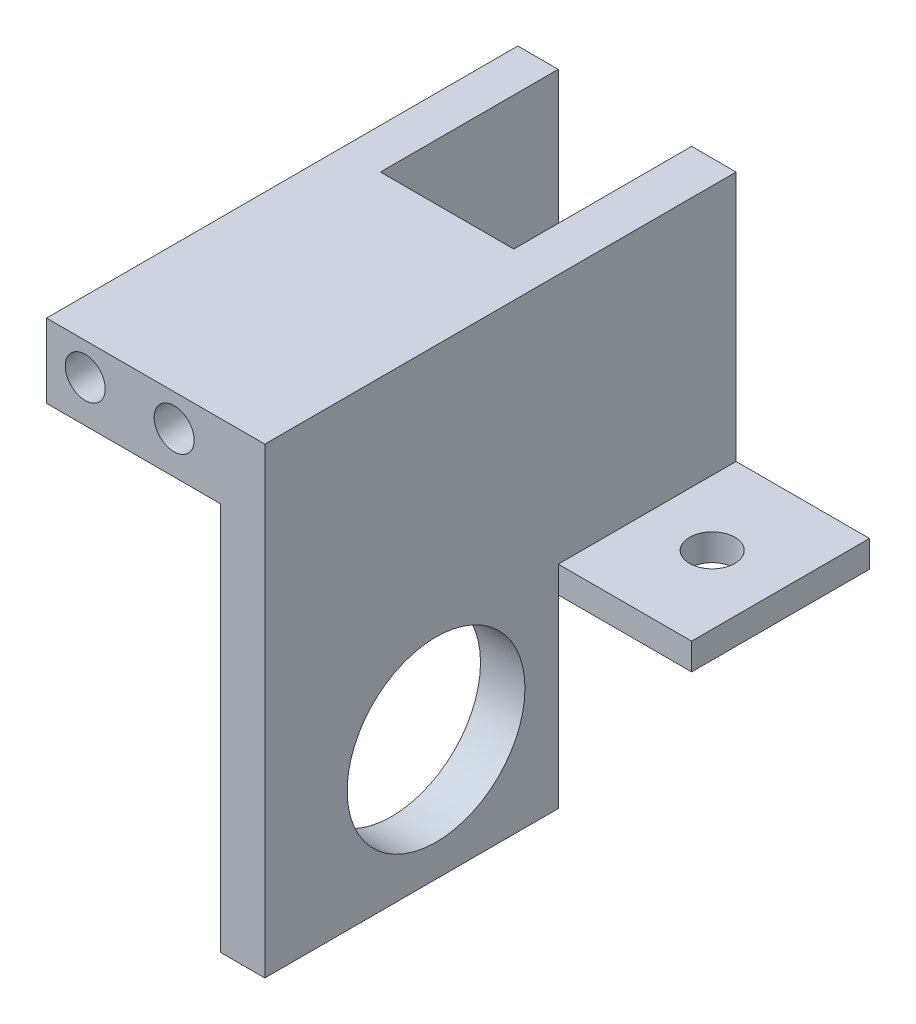
SolidWorks part; units mm, degrees
ref_plane "前视基准面" through (0, 0, 0) normal (0, 0, 1) x (1, 0, 0)
ref_plane "上视基准面" through (0, 0, 0) normal (0, 1, 0) x (1, 0, 0)
ref_plane "右视基准面" through (0, 0, 0) normal (1, 0, 0) x (0, 0, -1)
other "Configuration Table"
sketch "草图1" plane through (0, 0, 0) normal (0, 0, 1) x (1, 0, 0)
  line L1 (-11.1667, -5) -> (11.1667, -5)
  line L2 (-11.1667, -5) -> (-11.1667, 5)
  line L3 (-11.1667, 5) -> (11.1667, 5)
  line L4 (11.1667, -5) -> (11.1667, 5)
  line L5 (-11.1667, -5) -> (11.1667, 5) construction
  line L6 (-11.1667, 5) -> (11.1667, -5) construction
  point P0 (0, 0)
  dimension "D1" = 10
extrude "凸台-拉伸1" add sketch "草图1" along normal blind 30
sketch "草图2" plane through (0, -5, 0) normal (0, -1, 0) x (1, 0, 0)
  line L0 (-10.0833, 30.4566) -> (-10.0833, 0)
  line L1 (-10.0833, 30) -> (-10.0833, 38.1808) construction
  line L2 (-11.1667, 0) -> (11.1667, 0) construction
sketch "草图3" plane through (0, 0, 30) normal (0, 0, 1) x (1, 0, 0)
  line L0 (-9.2333, 0.05) -> (-9.2333, -5.0113)
  line L2 (9.4667, -5) -> (9.4667, 0.05)
  circle A0 centre (5.1167, -0.3) radius 2.25
  circle A1 centre (-4.8833, -0.3) radius 2.25
  arc A3 (9.4667, 0.05) -> (7.4667, 2.05) centre (7.4667, 0.05) ccw
  arc A4 (-9.2333, 0.05) -> (-6.4511, 1.8907) centre (-7.2333, 0.05) cw
sketch "草图4" plane through (0, -5, 0) normal (0, -1, 0) x (1, 0, 0)
  line L1 (-11.1667, 30) -> (-10.0833, 30)
  line L2 (-11.1667, 30) -> (-11.1667, 0)
  line L3 (-11.1667, 0) -> (-10.0833, 0)
  line L4 (-10.0833, 30) -> (-10.0833, 0)
extrude "切除-拉伸1" cut sketch "草图4" against normal blind 30
extrude "切除-拉伸2" cut sketch "草图3" against normal blind 15 contours A1 | A0 region at (-4.8833, -0.3, 30)
sketch "草图5" plane through (0, 0, 30) normal (0, 0, 1) x (1, 0, 0)
  line L0 (9.4667, -5) -> (9.4667, 0.05) construction
  line L1 (-9.2333, -5.0113) -> (9.4667, -5.0113)
  line L2 (-9.2333, -5.0113) -> (-9.2333, 3.3044)
  line L3 (-9.2333, 3.3044) -> (9.4667, 3.3044)
  line L4 (9.4667, -5.0113) -> (9.4667, 3.3044)
extrude "切除-拉伸3" cut sketch "草图5" against normal blind 30 flip side to cut
sketch "草图6" plane through (9.4667, 0, 0) normal (1, 0, 0) x (0, 0, -1)
  line L0 (22.3266, -2.313) -> (13.2059, -2.313) construction
sketch "草图7" plane through (0, 3.3044, 0) normal (0, 1, 0) x (1, 0, 0)
  arc A0 (-18.3547, 13) -> (-15.8066, 10.45) centre (-15.8066, 12.9981) cw
sketch "草图10" plane through (0, 0, 0) normal (0, 0, -1) x (-1, 0, 0)
  line L4 (-9.4667, -5) -> (9.2333, -5)
  line L5 (9.2333, -5) -> (9.2333, 3.3044)
  line L6 (9.2333, 3.3044) -> (-9.4667, 3.3044)
  line L7 (-9.4667, 3.3044) -> (-9.4667, -5)
  line L8 (-9.4667, -5) -> (9.2333, -5)
  line L9 (9.2333, -5) -> (9.2333, 3.3044)
  line L10 (9.2333, 3.3044) -> (-9.4667, 3.3044)
  line L11 (-9.4667, 3.3044) -> (-9.4667, -5)
  dimension "D1" = 0
extrude "凸台-拉伸2" add sketch "草图10" along normal blind 18
sketch "草图11" plane through (9.4667, 0, 0) normal (1, 0, 0) x (0, 0, -1)
  line L1 (18, -5) -> (-2, -5)
  line L2 (18, -5) -> (18, -2.313)
  line L3 (18, -2.313) -> (-2, -2.313)
  line L4 (-2, -5) -> (-2, -2.313)
  dimension "D1" = 20
extrude "切除-拉伸5" cut sketch "草图11" against normal through all
sketch "草图12" plane through (0, -2.313, 0) normal (0, -1, 0) x (1, 0, 0)
  line L0 (-9.2333, -12.9981) -> (9.4667, -12.9981)
  line L1 (-9.2333, -18) -> (-9.2333, 2) construction
  line L2 (9.4667, -200022.3266) -> (9.4667, 199986.7941) construction
  circle A0 centre (-4.7333, -12.9981) radius 2.5481
  circle A1 centre (4.9667, -12.9981) radius 2.5481
  point P5 (-4.7333, -12.9981)
  point P8 (4.9667, -12.9981)
  point P11 (0.1167, -12.9981)
  dimension "D1" = 4.5
  dimension "D2" = 4.5
extrude "切除-拉伸6" cut sketch "草图12" against normal through all contours L0 A0 | L0 A0 | L0 A1 | L0 A1 region at (-4.7333, -2.313, -11.9167) region at (4.9667, -2.313, -11.9167) region at (4.9667, -2.313, -14.0796) region at (-4.7333, -2.313, -14.0796)
sketch "草图13" plane through (0, 3.3044, 0) normal (0, 1, 0) x (1, 0, 0)
  line L0 (-9.2333, 18) -> (-9.2333, -30) construction
  line L1 (9.4667, 18) -> (-9.2333, 18)
  line L2 (9.4667, 18) -> (9.4667, 23)
  line L3 (9.4667, 23) -> (-9.2333, 23)
  line L4 (-9.2333, 18) -> (-9.2333, 23)
extrude "凸台-拉伸3" add sketch "草图13" against normal up to surface (5.6174 mm away) up to face at (-4.7333, -2.313, -15.5463)
sketch "草图14" plane through (0, 3.3044, 0) normal (0, 1, 0) x (1, 0, 0)
  line L1 (-4, -5.4) -> (4, -5.4)
  line L2 (-4, -5.4) -> (-4, -10.4)
  line L3 (-4, -10.4) -> (4, -10.4)
  line L4 (4, -5.4) -> (4, -10.4)
  dimension "D1" = 4
  dimension "D2" = 4
  dimension "D3" = 5.4
  dimension "D4" = 5
sketch "草图15" plane through (0, -5, 0) normal (0, -1, 0) x (1, 0, 0)
  line L1 (-9.2333, 2) -> (9.4667, 2)
  line L2 (-9.2333, 2) -> (-9.2333, -23)
  line L3 (-9.2333, -23) -> (9.4667, -23)
  line L4 (9.4667, 2) -> (9.4667, -23)
extrude "切除-拉伸7" cut sketch "草图15" against normal through all
sketch "草图16" plane through (0, 3.3044, 0) normal (0, 1, 0) x (1, 0, 0)
  line L0 (10.3167, -29.9) -> (10.3167, -1.7297)
sketch "草图17" plane through (0, 3.3044, 0) normal (0, 1, 0) x (1, 0, 0)
  line L0 (10.3167, -29.9) -> (10.3167, -1.7297) construction
  line L1 (9.4667, -2) -> (15.3167, -2)
  line L2 (9.4667, -2) -> (9.4667, -30)
  line L3 (9.4667, -30) -> (15.3167, -30)
  line L4 (15.3167, -2) -> (15.3167, -30)
  dimension "D1" = 5
sketch "草图18" plane through (9.4667, 0, 0) normal (1, 0, 0) x (0, 0, -1)
  line L4 (-2, -5) -> (-2, 3.3044)
  line L5 (-2, 3.3044) -> (-30, 3.3044)
  line L6 (-30, 3.3044) -> (-30, -5)
  line L7 (-30, -5) -> (-2, -5)
  line L8 (-2, -5) -> (-2, 3.3044)
  line L9 (-2, 3.3044) -> (-30, 3.3044)
  line L10 (-30, 3.3044) -> (-30, -5)
  line L11 (-30, -5) -> (-2, -5)
  dimension "D1" = 0
extrude "凸台-拉伸5" add sketch "草图18" along normal blind 0.85
sketch "草图20" plane through (0, 3.3044, 0) normal (0, 1, 0) x (1, 0, 0)
  line L1 (10.3167, -30) -> (15.3167, -30)
  line L2 (10.3167, -30) -> (10.3167, -2)
  line L3 (10.3167, -2) -> (15.3167, -2)
  line L4 (15.3167, -30) -> (15.3167, -2)
extrude "凸台-拉伸6" add sketch "草图20" against normal blind 52
sketch "草图22" plane through (15.3167, 0, 0) normal (1, 0, 0) x (0, 0, -1)
  circle A0 centre (-10.7419, -35.1) radius 10
  dimension "D1" = 20
sketch "草图23" plane through (0, 0, 2) normal (0, 0, -1) x (-1, 0, 0)
  line L6 (9.2333, 3.3044) -> (-15.3167, 3.3044)
  line L7 (-15.3167, 3.3044) -> (-15.3167, -48.6956)
  line L8 (-15.3167, -48.6956) -> (-10.3167, -48.6956)
  line L9 (-10.3167, -48.6956) -> (-10.3167, -5)
  line L10 (-10.3167, -5) -> (9.2333, -5)
  line L11 (9.2333, -5) -> (9.2333, 3.3044)
  line L12 (9.2333, 3.3044) -> (-15.3167, 3.3044)
  line L13 (-15.3167, 3.3044) -> (-15.3167, -48.6956)
  line L14 (-15.3167, -48.6956) -> (-10.3167, -48.6956)
  line L15 (-10.3167, -48.6956) -> (-10.3167, -5)
  line L16 (-10.3167, -5) -> (9.2333, -5)
  line L17 (9.2333, -5) -> (9.2333, 3.3044)
  dimension "D1" = 0
extrude "凸台-拉伸7" add sketch "草图23" along normal blind 5
extrude "切除-拉伸8" cut sketch "草图22" against normal through all contours A0
sketch "草图24" plane through (0, 0, -3) normal (0, 0, -1) x (-1, 0, 0)
  line L0 (-10.3167, -5) -> (-10.3167, 3.3044)
  line L6 (9.2333, -5) -> (9.2333, 3.3044)
  line L7 (9.2333, 3.3044) -> (-15.3167, 3.3044)
  line L8 (-15.3167, 3.3044) -> (-15.3167, -48.6956)
  line L9 (-15.3167, -48.6956) -> (-10.3167, -48.6956)
  line L10 (-10.3167, -48.6956) -> (-10.3167, -5)
  line L11 (-10.3167, -5) -> (9.2333, -5)
  line L13 (-10.3167, 3.3044) -> (-15.3167, 3.3044)
  line L14 (-15.3167, 3.3044) -> (-15.3167, -48.6956)
  line L15 (-15.3167, -48.6956) -> (-10.3167, -48.6956)
  line L16 (-10.3167, -48.6956) -> (-10.3167, -5)
  dimension "D1" = 0
extrude "凸台-拉伸8" add sketch "草图24" along normal blind 20
sketch "草图28" plane through (0, -48.6956, 0) normal (0, -1, 0) x (1, 0, 0)
  line L1 (10.3167, -3) -> (15.3167, -3)
  line L2 (10.3167, -3) -> (10.3167, -23)
  line L3 (10.3167, -23) -> (15.3167, -23)
  line L4 (15.3167, -3) -> (15.3167, -23)
sketch "草图29" plane through (0, 0, -23) normal (0, 0, -1) x (-1, 0, 0)
  line L0 (-21.3498, -27.8856) -> (-1.9409, -27.8856)
  line L1 (-9.4667, 3.3044) -> (-15.3167, 3.3044) construction
  dimension "D1" = 31.19
sketch "草图30" plane through (0, -48.6956, 0) normal (0, -1, 0) x (1, 0, 0)
  line L1 (10.3167, -23) -> (15.3167, -23)
  line L2 (10.3167, -23) -> (10.3167, -3)
  line L3 (10.3167, -3) -> (15.3167, -3)
  line L4 (15.3167, -23) -> (15.3167, -3)
extrude "切除-拉伸10" cut sketch "草图30" against normal up to vertex (20.81 mm away) up to point (21.3498, -27.8856, -23)
sketch "草图31" plane through (15.3167, 0, 0) normal (1, 0, 0) x (0, 0, -1)
  line L0 (23, 3.3044) -> (23, -27.8856) construction
  line L1 (3, -27.8856) -> (23, -27.8856)
  line L2 (3, -27.8856) -> (3, -24.8856)
  line L3 (3, -24.8856) -> (23, -24.8856)
  line L4 (23, -27.8856) -> (23, -24.8856)
  dimension "D1" = 3
extrude "凸台-拉伸9" add sketch "草图31" along normal blind 15 and the other way blind 20
sketch "草图32" plane through (0, -24.8856, 0) normal (0, 1, 0) x (1, 0, 0)
  line L0 (-4.6833, 13) -> (30.3167, 13)
  line L1 (-4.6833, 23) -> (-4.6833, 3) construction
  line L2 (30.3167, 23) -> (30.3167, 3) construction
  line L3 (12.8167, 3) -> (12.8167, 28.2983)
  line L4 (10.3167, 3) -> (15.3167, 3) construction
  circle A0 centre (3.0008, 13) radius 2.55
  circle A1 centre (22.6325, 13) radius 2.55
  dimension "D1" = 5.1
extrude "切除-拉伸11" cut sketch "草图32" against normal through all contours A0 | A1
sketch "草图33" plane through (0, 3.3044, 0) normal (0, 1, 0) x (1, 0, 0)
  line L1 (-9.2333, 3) -> (-4.6833, 3)
  line L2 (-9.2333, 3) -> (-9.2333, 23)
  line L3 (-9.2333, 23) -> (-4.6833, 23)
  line L4 (-4.6833, 3) -> (-4.6833, 23)
extrude "凸台-拉伸10" add sketch "草图33" against normal up to surface (31.19 mm away) up to face at (12.8167, -27.8856, -9.6667)
